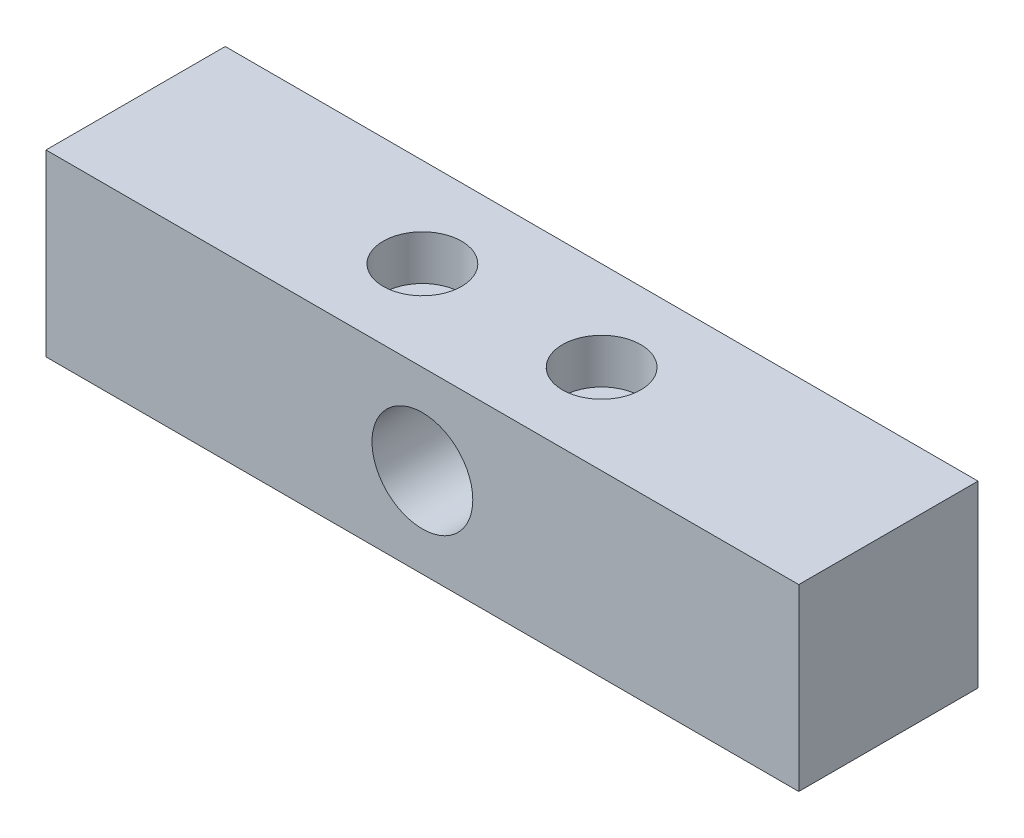
SolidWorks part; units mm, degrees
material "ABS"
ref_plane "Front Plane" through (0, 0, 0) normal (0, 0, 1) x (1, 0, 0)
ref_plane "Top Plane" through (0, 0, 0) normal (0, 1, 0) x (1, 0, 0)
ref_plane "Right Plane" through (0, 0, 0) normal (1, 0, 0) x (0, 0, -1)
sketch "Sketch1" plane through (0, 0, 0) normal (0, 0, 1) x (1, 0, 0)
  line L0 (38.1, 0) -> (-38.1, 0) construction
  line L1 (53.34, 12.7) -> (-53.34, 12.7)
  line L2 (53.34, 12.7) -> (53.34, -12.7)
  line L3 (53.34, -12.7) -> (-53.34, -12.7)
  line L4 (-53.34, 12.7) -> (-53.34, -12.7)
  line L5 (53.34, 12.7) -> (-53.34, -12.7) construction
  line L6 (53.34, -12.7) -> (-53.34, 12.7) construction
  circle A0 centre (38.1, 0) radius 8.128
  circle A1 centre (-38.1, 0) radius 8.128
  point P0 (0, 0)
  point P10 (0, 0)
  dimension "D1" = 16.256
  dimension "D2" = 76.2
  dimension "D3" = 15.24
  dimension "D4" = 12.7
extrude "Boss-Extrude1" add sketch "Sketch1" along normal blind 25.4 contours L3 L4 L1 L2
extrude "Cut-Extrude1" cut sketch "Sketch1<3>" along normal blind 19.05 contours A1 | A0 region at (-38.1, 0, 0)
sketch "Sketch1<3>" plane through (0, 0, 0) normal (0, 0, 1) x (1, 0, 0) same geometry as "Sketch1"
hole_wizard "CBORE for 1/4 Binding Head Machine Screw1" positions "Sketch2" profile "Sketch3" counterbore size "1/4" standard "ANSI Inch" end condition up to next
sketch "Sketch2" plane through (0, 0, 25.4) normal (0, 0, 1) x (1, 0, 0)
  point P0 (0, 0)
sketch "Sketch3" plane through (0, 0, 25.4) normal (1, 0, 0) x (0, -1, 0)
  line L0 (0, 0) -> (0, 25.4)
  line L1 (0, 25.4) -> (3.3782, 25.4)
  line L3 (3.3782, 25.4) -> (3.3782, 19.05)
  line L4 (3.3782, 19.05) -> (7.1437, 19.05)
  line L5 (7.1437, 19.05) -> (7.1437, 0)
  line L7 (7.1437, 0) -> (0, 0)
  line L11 (0, -6.35) -> (0, 107.95) construction
  dimension "Thru Hole Dia." = 6.7564
  dimension "Thru Hole Depth" = 25.4
  dimension "C'Bore Dia." = 14.2875
  dimension "C'Bore Depth" = 19.05
hole_wizard "CBORE for 1/4 Socket Head Cap Screw1" positions "Sketch4" profile "Sketch5" counterbore size "1/4" standard "ANSI Inch" end condition up to next
sketch "Sketch4" plane through (0, 12.7, 0) normal (0, 1, 0) x (1, 0, 0)
  line L0 (-12.7, -12.7) -> (12.7, -12.7)
  line L1 (53.34, -25.4) -> (-53.34, -25.4) construction
  line L2 (0, 0) -> (0, -25.4)
  line L3 (53.34, 0) -> (-53.34, 0) construction
  point P0 (12.7, -12.7)
  point P2 (-12.7, -12.7)
  point P16 (0, -12.7)
  dimension "D1" = 25.4
sketch "Sketch5" plane through (12.7, 12.7, 12.7) normal (1, 0, 0) x (0, 0, 1)
  line L0 (0, 0) -> (0, 25.4)
  line L1 (0, 25.4) -> (3.3782, 25.4)
  line L3 (3.3782, 25.4) -> (3.3782, 6.35)
  line L4 (3.3782, 6.35) -> (5.5562, 6.35)
  line L5 (5.5562, 6.35) -> (5.5563, 0)
  line L7 (5.5563, 0) -> (0, 0)
  line L11 (0, -6.35) -> (0, 107.95) construction
  dimension "Thru Hole Dia." = 6.7564
  dimension "Thru Hole Depth" = 25.4
  dimension "C'Bore Dia." = 11.1125
  dimension "C'Bore Depth" = 6.35
